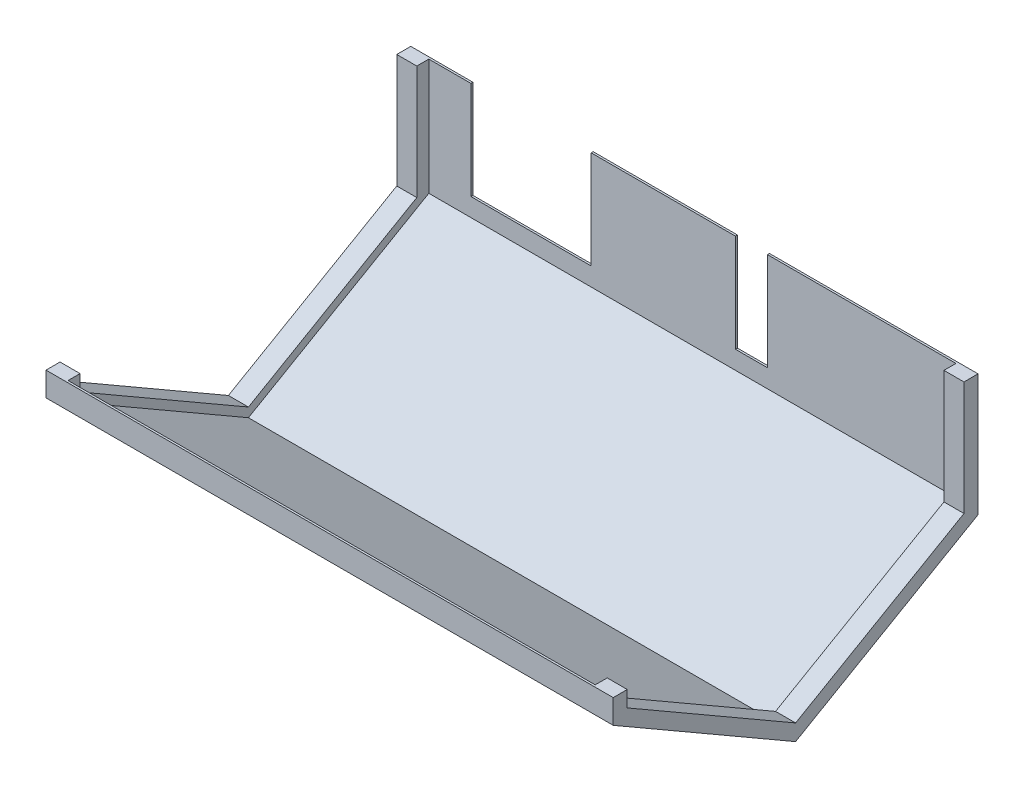
SolidWorks part; units mm, degrees
note: The reader was unsure of these and kept them because the rebuilt part matched: shared geometry of "Эскиз5<2>".
ref_plane "Спереди" through (0, 0, 0) normal (0, 0, 1) x (1, 0, 0)
ref_plane "Сверху" through (0, 0, 0) normal (0, 1, 0) x (1, 0, 0)
ref_plane "Справа" through (0, 0, 0) normal (1, 0, 0) x (0, 0, -1)
other "Configuration Table"
sketch "Эскиз2" plane through (0, 0, 0) normal (1, 0, 0) x (0, 0, -1)
  line L0 (4500, 2750) -> (4500, -2921.2813) construction
  line L1 (9000, 2750) -> (0, 2750) construction
  line L2 (4500, -2921.2813) -> (9050, -294.3376)
  line L3 (9050, -294.3376) -> (9050, 2750)
  line L4 (9050, 2750) -> (9000, 2750)
  line L5 (9000, 2750) -> (9000, -150)
  line L6 (9000, -150) -> (4500, -2748.0762)
  line L7 (9000, -150) -> (9000, 2750) construction
  line L8 (9000, -150) -> (0, -150) construction
  line L9 (0, -150) -> (4500, -2748.0762)
  line L10 (0, 2750) -> (0, -150)
  line L11 (-50, 2750) -> (0, 2750)
  line L12 (-50, -294.3376) -> (-50, 2750)
  line L13 (4500, -2921.2813) -> (-50, -294.3376)
  line L14 (7000, -150) -> (7000, -1304.7005) construction
  dimension "D1" = 150
  dimension "D2" = 50
  dimension "D3" = 5671.2813
  dimension "D4" = 2598.0762
  dimension "D5" = 2500
  dimension "D6" = 1154.7005
  dimension "D7" = 30
extrude "Бобышка-Вытянуть1" add sketch "Эскиз2" against normal up to surface (13150 mm away)
sketch "Эскиз5" plane through (0, 0, 0) normal (1, 0, 0) x (0, 0, -1)
  line L0 (4500, -2921.2813) -> (4500, 3507.5434) construction
  line L1 (-50, 2750) -> (-50, -294.3376)
  line L2 (-50, -294.3376) -> (4500, -2921.2813)
  line L3 (-50, 2750) -> (300, 2750)
  line L4 (300, 2750) -> (300, -92.265)
  line L5 (300, -92.265) -> (4500, -2517.1361)
  line L6 (8700, -92.265) -> (4500, -2517.1361)
  line L7 (8700, 2750) -> (8700, -92.265)
  line L8 (9050, 2750) -> (8700, 2750)
  line L9 (9050, 2750) -> (9050, -294.3376)
  line L10 (9050, -294.3376) -> (4500, -2921.2813)
  dimension "D1" = 350
  dimension "D2" = 350
extrude "Бобышка-Вытянуть2" add sketch "Эскиз5" along normal blind 500
extrude "Бобышка-Вытянуть3" add sketch "Эскиз5<2>" against normal blind 500 from surface at -13150
sketch "Эскиз5<2>" plane through (0, 0, 0) normal (1, 0, 0) x (0, 0, -1) same geometry as "Эскиз5"
sketch "Эскиз4" plane through (0, 0, -9050) normal (0, 0, -1) x (-1, 0, 0)
  line L0 (9000, 2950) -> (9000, 2750) construction
  line L1 (5500, 305.6624) -> (4700, 305.6624)
  line L2 (5500, 305.6624) -> (5500, 3008.1407)
  line L3 (5500, 3008.1407) -> (4700, 3008.1407)
  line L4 (4700, 305.6624) -> (4700, 3008.1407)
  line L5 (9100, 2984.0805) -> (12100, 2984.0805)
  line L6 (9100, 2984.0805) -> (9100, 305.6624)
  line L7 (9100, 305.6624) -> (12100, 305.6624)
  line L8 (12100, 2984.0805) -> (12100, 305.6624)
  line L9 (13650, -294.3376) -> (13650, 2750) construction
  line L10 (13650, -294.3376) -> (-500, -294.3376) construction
  dimension "D1" = 100
  dimension "D2" = 3000
  dimension "D3" = 1550
  dimension "D4" = 600
extrude "Вырез-Вытянуть2" cut sketch "Эскиз4" against normal blind 460
sketch "Эскиз7" plane through (0, 0, 50) normal (0, 0, 1) x (1, 0, 0)
  line L1 (-14440.1641, 3533.1696) -> (1269.69, 3533.1696)
  line L2 (-14440.1641, 3533.1696) -> (-14440.1641, 305.6624)
  line L3 (-14440.1641, 305.6624) -> (1269.69, 305.6624)
  line L4 (1269.69, 3533.1696) -> (1269.69, 305.6624)
  line L5 (-12100, 305.6624) -> (-9100, 305.6624) construction
extrude "Вырез-Вытянуть4" cut sketch "Эскиз7" against normal blind 670
